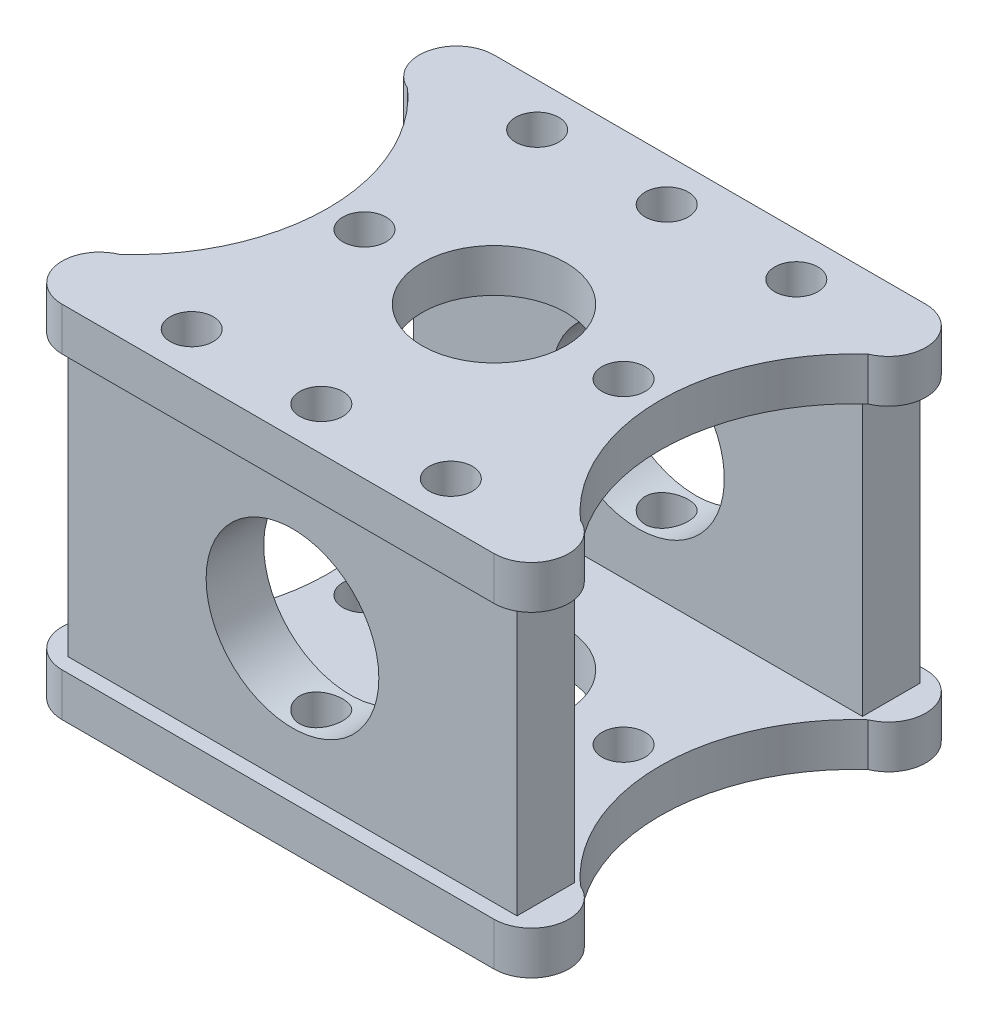
SolidWorks part; units mm, degrees
ref_plane "Plan de face" through (0, 0, 0) normal (0, 0, 1) x (1, 0, 0)
ref_plane "Plan de dessus" through (0, 0, 0) normal (0, 1, 0) x (1, 0, 0)
ref_plane "Plan de droite" through (0, 0, 0) normal (1, 0, 0) x (0, 0, -1)
sketch "Esquisse1" plane through (0, 0, 0) normal (0, 1, 0) x (1, 0, 0)
  line L0 (-15, 15) -> (15, 15)
  line L1 (-15, -15) -> (15, -15)
  line L2 (-16, 10) -> (16, 10) construction
  line L3 (-16, -10) -> (16, -10) construction
  arc A0 (-15, 15) -> (-16, 10) centre (-15, 12.4) ccw
  arc A1 (-16, 10) -> (-16, -10) centre (-25, 0) cw
  arc A2 (-16, -10) -> (-15, -15) centre (-15, -12.4) ccw
  arc A3 (15, 15) -> (16, 10) centre (15, 12.4) cw
  arc A4 (16, 10) -> (16, -10) centre (25, 0) ccw
  arc A5 (16, -10) -> (15, -15) centre (15, -12.4) cw
  circle A6 centre (0, 0) radius 5
  circle A7 centre (9, 0) radius 1.5
  circle A8 centre (-9, 0) radius 1.5
  circle A9 centre (-9, 12) radius 1.5
  circle A10 centre (9, 12) radius 1.5
  circle A11 centre (-9, -12) radius 1.5
  circle A12 centre (9, -12) radius 1.5
  circle A13 centre (0, -12) radius 1.5
  circle A14 centre (0, 12) radius 1.5
  dimension "D11" = 9
  dimension "D13" = 3
  dimension "D17" = 25
  dimension "D1" = 30
  dimension "D2" = 32
  dimension "D3" = 32
  dimension "D4" = 30
  dimension "D5" = 5
  dimension "D6" = 15
  dimension "D7" = 5
  dimension "D8" = 30
  dimension "D9" = 16
  dimension "D10" = 16
  dimension "D12" = 9
  dimension "D14" = 3
  dimension "D15" = 3
  dimension "D16" = 3
  dimension "D18" = 25
  dimension "D19" = 9
  dimension "D20" = 18
  dimension "D21" = 9
  dimension "D22" = 18
extrude "Boss.-Extru.1" add sketch "Esquisse1" along normal blind 25
sketch "Esquisse2" plane through (0, 0, 0) normal (1, 0, 0) x (0, 0, -1)
  line L0 (19.0099, 22) -> (-19.6225, 22) construction
  line L1 (19.0099, 3) -> (-19.6225, 3) construction
  line L2 (-10, 0) -> (10, 0) construction
  line L3 (10, 25) -> (-10, 25) construction
  line L5 (10, 22) -> (-10, 22)
  line L6 (10, 22) -> (10, 3)
  line L7 (10, 3) -> (-10, 3)
  line L8 (-10, 22) -> (-10, 3)
  line L9 (18.5607, 22) -> (14, 22)
  line L10 (18.5607, 22) -> (18.5607, 3)
  line L11 (18.5607, 3) -> (14, 3)
  line L12 (14, 22) -> (14, 3)
  line L13 (-17.8256, 22) -> (-14, 22)
  line L14 (-17.8256, 22) -> (-17.8256, 3)
  line L15 (-17.8256, 3) -> (-14, 3)
  line L16 (-14, 22) -> (-14, 3)
  dimension "D1" = 3
  dimension "D2" = 3
  dimension "D3" = 20
  dimension "D4" = 10
  dimension "D5" = 4
  dimension "D6" = 4
extrude "Enlèv. mat.-Extru.1" cut sketch "Esquisse2" against normal blind 25 and the other way blind 25
sketch "Esquisse3" plane through (0, 0, 14) normal (0, 0, 1) x (1, 0, 0)
  line L0 (17.0494, 22) -> (-17.0494, 22) construction
  line L1 (-15.6, 22) -> (-23.9707, 22)
  line L2 (-15.6, 22) -> (-15.6, 3)
  line L3 (-15.6, 3) -> (-23.9707, 3)
  line L4 (-23.9707, 22) -> (-23.9707, 3)
  line L5 (-17.6, 25) -> (-17.6, 0) construction
  line L6 (15.6, 22) -> (24.975, 22)
  line L7 (15.6, 22) -> (15.6, 3)
  line L8 (15.6, 3) -> (24.975, 3)
  line L9 (24.975, 22) -> (24.975, 3)
  line L10 (17.6, 0) -> (17.6, 25) construction
  line L11 (15, 3) -> (15, 0) construction
  circle A0 centre (0, 12.5) radius 6
  dimension "D6" = 12
  dimension "D1" = 2
  dimension "D2" = 2
  dimension "D3" = 19
  dimension "D4" = 19
  dimension "D5" = 12.5
  dimension "D7" = 15
extrude "Enlèv. mat.-Extru.2" cut sketch "Esquisse3" against normal blind 30
